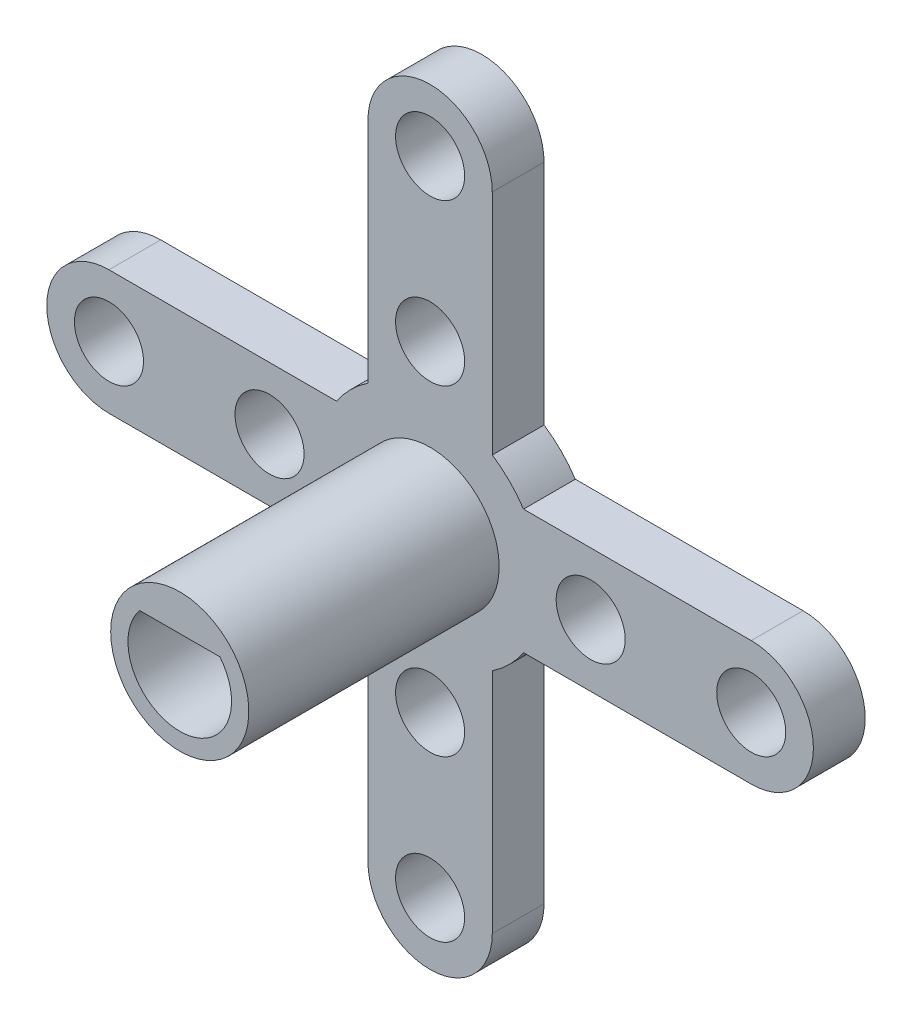
SolidWorks part; units mm, degrees
ref_plane "Přední rovina" through (0, 0, 0) normal (0, 0, 1) x (1, 0, 0)
ref_plane "Horní rovina" through (0, 0, 0) normal (0, 1, 0) x (1, 0, 0)
ref_plane "Pravá rovina" through (0, 0, 0) normal (1, 0, 0) x (0, 0, -1)
sketch "Sketch1" plane through (0, 0, 0) normal (0, 0, 1) x (1, 0, 0)
  line L0 (0, 9.3) -> (0, -9.3) construction
  line L1 (1.8, 9.3) -> (1.8, -9.3)
  line L2 (-1.8, 9.3) -> (-1.8, -9.3)
  line L3 (-9.3, 0) -> (9.3, 0) construction
  line L4 (-9.3, 1.8) -> (9.3, 1.8)
  line L5 (-9.3, -1.8) -> (9.3, -1.8)
  arc A0 (1.8, 9.3) -> (-1.8, 9.3) centre (0, 9.3) ccw
  arc A1 (-1.8, -9.3) -> (1.8, -9.3) centre (0, -9.3) ccw
  arc A2 (-9.3, 1.8) -> (-9.3, -1.8) centre (-9.3, 0) ccw
  arc A3 (9.3, -1.8) -> (9.3, 1.8) centre (9.3, 0) ccw
  circle A4 centre (0, 0) radius 1
  circle A7 centre (0, 4.65) radius 1
  circle A8 centre (0, 9.3) radius 1
  circle A9 centre (0, 0) radius 3.25
  point P3 (0, 0)
  point P10 (0, 0)
  dimension "D3" = 2
  dimension "D4" = 1.8
  dimension "D5" = 1.8
  dimension "D6" = 2
  dimension "D7" = 2
  dimension "D10" = 6.5
  dimension "D1" = 18.6
  dimension "D2" = 18.6
  dimension "D8" = 4.65
  dimension "D9" = 4.65
extrude "Boss-Extrude1" add sketch "Sketch1" along normal blind 1.5 contours L4 A9 L5 L2 | L5 A9 L2 | L2 A9 L1 L5 | L1 A9 L5 | L5 A9 L4 L1 | L4 A9 L1 | L1 A9 L2 L4 | L2 A9 L4 | L2 L5 L1 L4 A4 | A9 L1 A0 L2 A8 A7 | A9 region at (0, 6.8821, 0) region at (2.1218, 2.1218, 0) region at (0, 2.4476, 0) region at (2.4476, 0, 0) region at (1.7491, 0, 0) region at (-2.1218, 2.1218, 0) region at (2.1218, -2.1218, 0) region at (0, -2.4476, 0) region at (-2.4476, 0, 0) region at (-2.1218, -2.1218, 0)
pattern_circular "CirPattern1" count 4 over 360 about axis through (0, 0, 1.5) along (0, 0, 1) of "Boss-Extrude1"
sketch "Sketch2" plane through (0, 0, 0) normal (0, 0, -1) x (-1, 0, 0)
  line L1 (2.05, 1.7571) -> (-2.05, 1.7571)
  line L2 (2.05, -1.7571) -> (-2.05, -1.7571)
  circle A0 centre (0, 0) radius 2.7
  dimension "D1" = 5.4
  dimension "D2" = 4.1
  dimension "D3" = 4.1
extrude "Boss-Extrude2" [suppressed] add sketch "Sketch2" along normal blind 2
sketch "Sketch3" plane through (0, 0, 1.5) normal (0, 0, 1) x (1, 0, 0)
  line L0 (-1.1608, 0.95) -> (1.1608, 0.95)
  line L1 (0, -1.5) -> (0, 0) construction
  circle A0 centre (0, 0) radius 2
  circle A1 centre (0, 0) radius 1.5
  dimension "D1" = 4
  dimension "D2" = 3
  dimension "D3" = 2.45
extrude "Boss-Extrude3" add sketch "Sketch3" along normal blind 7.25 contours A0 A1 | L0 A1 | L0 region at (0, 1.1739, 1.5) region at (-1.9434, 0, 1.5)
